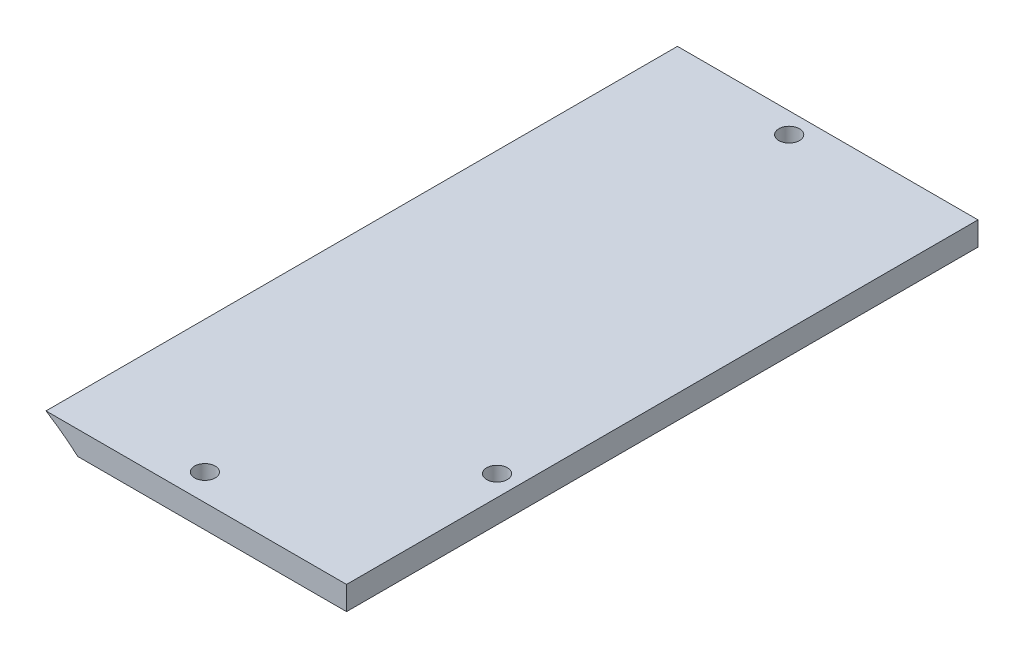
SolidWorks part; units mm, degrees
material "Acrylic (Medium-high impact)"
ref_plane "Front Plane" through (0, 0, 0) normal (0, 0, 1) x (1, 0, 0)
ref_plane "Top Plane" through (0, 0, 0) normal (0, 1, 0) x (1, 0, 0)
ref_plane "Right Plane" through (0, 0, 0) normal (1, 0, 0) x (0, 0, -1)
ref_axis "Axis1" through (0, 0, -5.35) along (0, 0, 1)
sketch "Sketch1" plane through (0, 0, 0) normal (0, 0, 1) x (1, 0, 0)
  circle A0 centre (0, 0) radius 38
  circle A1 centre (0, 0) radius 40
  dimension "D1" = 76
  dimension "D2" = 2
extrude "Boss-Extrude1" add sketch "Sketch1" along normal blind 200
ref_plane "Plane1" through (0, 0, 180) normal (0, 0, 1) x (1, 0, 0)
sketch "Sketch2" plane through (0, 0, 180) normal (0, 0, 1) x (1, 0, 0)
  circle A0 centre (0, 0) radius 40 construction
  circle A1 centre (0, 0) radius 40
extrude "Boss-Extrude2" add sketch "Sketch2" along normal blind 2
sketch "Sketch3" plane through (0, 0, 0) normal (0, 0, -1) x (-1, 0, 0)
  line L0 (-21.0713, -34) -> (-72, -34)
  line L1 (-72, -34) -> (-72, -30)
  line L2 (-72, -30) -> (-26.4575, -30)
  line L3 (-21.0713, 34) -> (-72, 34)
  line L4 (-72, 30) -> (-26.4575, 30)
  line L5 (-72, 34) -> (-72, 30)
  line L6 (-40, -15.2942) -> (-40, 13.2229) construction
  line L8 (0, 0) -> (-59.0266, 0) construction
  circle A1 centre (0, 0) radius 40 construction
  arc A2 (-21.0713, 34) -> (-26.4575, 30) centre (0, 0) ccw
  arc A3 (-26.4575, -30) -> (-21.0713, -34) centre (0, 0) ccw
  dimension "D1" = 60
  dimension "D2" = 4
  dimension "D3" = 32
extrude "Boss-Extrude3" add sketch "Sketch3" against normal blind 107
sketch "Sketch4" plane through (0, 0, 107) normal (0, 0, 1) x (1, 0, 0)
  line L2 (72, -34) -> (21.0713, -34) construction
  line L3 (21.0713, 34) -> (72, 34) construction
  line L4 (72, -34) -> (21.0713, -34)
  line L5 (21.0713, 34) -> (72, 34)
  line L6 (72, -34) -> (72, 34)
  circle A0 centre (0, 0) radius 40 construction
  arc A2 (21.0713, -34) -> (21.0713, 34) centre (0, 0) ccw
extrude "Boss-Extrude4" add sketch "Sketch4" along normal blind 2
sketch "Sketch5" plane through (0, 34, 0) normal (0, 1, 0) x (1, 0, 0)
  circle A5 centre (43.5, -102.5) radius 1.75 construction
  circle A6 centre (43.5, -102.5) radius 1.75
  circle A7 centre (43.5, -3.5) radius 1.75 construction
  circle A8 centre (43.5, -3.5) radius 1.75
  circle A9 centre (68.5, -78) radius 1.75 construction
  circle A10 centre (68.5, -78) radius 1.75
extrude "Cut-Extrude1" cut sketch "Sketch5" against normal through all
ref_plane "Plane2" through (0, 0, 0) normal (-0.7071, 0.7071, 0) x (0, 0, 1)
sketch "Sketch6" plane through (0, 0, 0) normal (-0.7071, 0.7071, 0) x (0, 0, 1)
  line L0 (200, -40) -> (200, 40) construction
  line L1 (200, -40) -> (200, 40) construction
  circle A0 centre (187, 0) radius 4
  dimension "D1" = 8
  dimension "D2" = 13
extrude "Cut-Extrude2" cut sketch "Sketch6" against normal up to next and the other way up to next
pattern_circular "CirPattern1" count 2 every 90 about axis through (0, 0, -5.35) along (0, 0, 1) of "Cut-Extrude2"
ref_plane "Plane3" through (-54, 0, 0) normal (1, 0, 0) x (0, 0, -1)
sketch "Sketch7" plane through (-54, 0, 0) normal (1, 0, 0) x (0, 0, -1)
  line L0 (0, 0) -> (-33.0452, 0) construction
  line L1 (-14, -11) -> (0, -11)
  line L2 (-14, -11) -> (-14, -13)
  line L3 (-14, -13) -> (0, -13)
  line L4 (0, -11) -> (0, -13)
  line L5 (0, -40) -> (0, 40) construction
  line L6 (0, 11) -> (0, 13)
  line L7 (-14, 13) -> (0, 13)
  line L8 (-14, 11) -> (-14, 13)
  line L9 (-14, 11) -> (0, 11)
  dimension "D1" = 2
  dimension "D2" = 14
  dimension "D3" = 22
extrude "Boss-Extrude5" add sketch "Sketch7" along normal up to surface (15.5422 mm away) up to face at (25.3934, 30.9059, 187.8976)
sketch "Sketch8" plane through (0, -13, 0) normal (0, -1, 0) x (1, 0, 0)
  line L6 (-37.8286, 14) -> (-37.8286, 0) construction
  line L7 (-37.8286, 0) -> (-54, 0) construction
  circle A0 centre (-49.7703, 5.0088) radius 1.75
  dimension "D3" = 3.5
  dimension "D1" = 11.9417
  dimension "D2" = 5.0088
extrude "Cut-Extrude3" cut sketch "Sketch8" against normal up to surface (26 mm away) up to face at (-45.9143, 13, 7)
fillet "Fillet1" radius 3 4 edges at (-54, 12, 0) (-54, -12, 0) (-54, -12, 14) (-54, 12, 14)
sketch "Sketch9" plane through (0, 11, 0) normal (0, -1, 0) x (1, 0, 0)
  circle A0 centre (-43.7703, 7.0088) radius 0.25
  circle A1 centre (-49.7703, 5.0088) radius 1.75 construction
  dimension "D1" = 6
  dimension "D2" = 2
  dimension "D3" = 0.5
extrude "Cut-Extrude4" cut sketch "Sketch9" against normal up to next
sketch "Sketch10" plane through (0, 0, 0) normal (0, 0, -1) x (-1, 0, 0)
  line L0 (-10, 38.7298) -> (-10, 36.6606)
  line L2 (10, 38.7298) -> (10, 36.6606)
  line L3 (-10, -36.6606) -> (-10, -38.7298)
  line L4 (10, -36.6606) -> (10, -38.7298)
  line L5 (-10, 36.6606) -> (10, 36.6606) construction
  line L6 (0, 36.6606) -> (0, 0) construction
  circle A0 centre (0, 0) radius 38 construction
  arc A1 (37.8286, 13) -> (-21.0713, 34) centre (0, 0) ccw construction
  arc A2 (-10, -36.6606) -> (10, -36.6606) centre (0, 0) ccw
  arc A3 (37.8286, 13) -> (-10, 38.7298) centre (0, 0) ccw
  arc A4 (10, 36.6606) -> (-10, 36.6606) centre (0, 0) ccw
  arc A5 (-21.0713, -34) -> (37.8286, -13) centre (0, 0) ccw construction
  arc A6 (-10, -38.7298) -> (37.8286, -13) centre (0, 0) ccw
  arc M9 (37.8286, 13) -> (-21.0713, 34) centre (0, 0) ccw
  arc M17 (-21.0713, -34) -> (37.8286, -13) centre (0, 0) ccw
  circle M22 centre (0, 0) radius 38
  dimension "D1" = 20
extrude "Boss-Extrude6" add sketch "Sketch10" along normal blind 2 contours L4 L3 M22 M17 | L2 L0 M9 M22 region at (0, 38.5641, 0) region at (0, -38.5641, 0)
sketch "Sketch11" plane through (0, 0, 200) normal (0, 0, 1) x (1, 0, 0)
  line L0 (72, 30) -> (26.4575, 30)
  line L1 (72, 30) -> (26.4575, 30) construction
  line L3 (72, -34) -> (72, 34)
  line L4 (72, 34) -> (21.0713, 34)
  line L5 (21.0713, -34) -> (72, -34)
  line L6 (72, -34) -> (72, 30)
  line L8 (21.0713, -34) -> (72, -34)
  circle A0 centre (0, 0) radius 40 construction
  arc A1 (26.4575, 30) -> (-1.9478, 39.9525) centre (0, 0) ccw
  arc A2 (-1.9478, 39.9525) -> (-1.9478, -39.9525) centre (-30.1608, 0) ccw
  arc A3 (21.0713, -34) -> (21.0713, 34) centre (0, 0) ccw
  arc A4 (26.4575, 30) -> (21.0713, 34) centre (0, 0) ccw
  arc A5 (-1.9478, -39.9525) -> (21.0713, -34) centre (0, 0) ccw
  circle M6 centre (0, 0) radius 40
  circle M7 centre (0, 0) radius 38
  dimension "D1" = 0
extrude "Cut-Extrude5" cut sketch "Sketch11" against normal through all contours A2 M6 | A1 M6 M7 | L8 L6 L0 M6 | M7 region at (53.241, -2.6088, 200) region at (35.4263, 15.992, 200) region at (-47.9452, 0, 200) region at (0, 0, 200)
sketch "Sketch12" plane through (0, 0, 109) normal (0, 0, 1) x (1, 0, 0)
  line L3 (26.4575, 30) -> (72, 30)
  line L4 (72, 30) -> (72, 34)
  line L5 (72, 34) -> (21.0713, 34)
  line L6 (26.4575, 30) -> (72, 30)
  line L7 (72, 30) -> (72, 34)
  line L8 (72, 34) -> (21.0713, 34)
  arc A1 (26.4575, 30) -> (21.0713, 34) centre (0, 0) ccw
  arc A2 (26.4575, 30) -> (21.0713, 34) centre (0, 0) ccw
  dimension "D1" = 0
extrude "Cut-Extrude6" cut sketch "Sketch12" against normal blind 2
